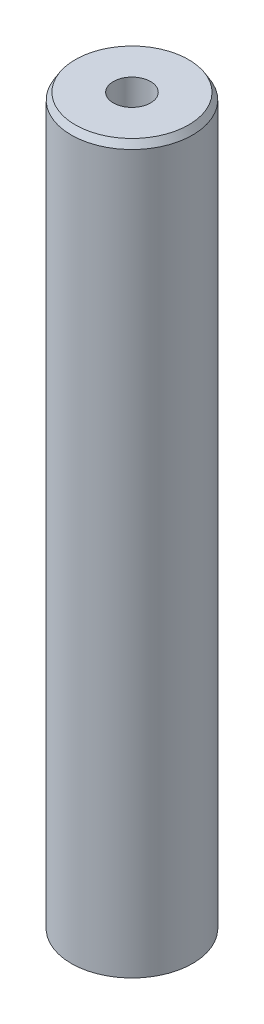
SolidWorks part; units mm, degrees
ref_plane "Front Plane" through (0, 0, 0) normal (0, 0, 1) x (1, 0, 0)
ref_plane "Top Plane" through (0, 0, 0) normal (0, 1, 0) x (1, 0, 0)
ref_plane "Right Plane" through (0, 0, 0) normal (1, 0, 0) x (0, 0, -1)
sketch "Sketch1" plane through (0, 0, 0) normal (0, 1, 0) x (1, 0, 0)
  circle A0 centre (0, 0) radius 50
  dimension "SHAFT_OD" = 100
extrude "Boss-Extrude1" add sketch "Sketch1" along normal blind 600
sketch "Sketch2" plane through (0, 0, 0) normal (0, 1, 0) x (1, 0, 0)
  circle A0 centre (0, 0) radius 15.3326
  dimension "BORE_D" = 30.6652
extrude "Cut-Extrude1" cut sketch "Sketch2" along normal through all
chamfer "Chamfer1" distance 5.542 angle 31.045 2 edges at (0, 600, 50) (0, 0, 50) first distance on face at (0, 600, 50) first distance on face at (0, 0, 15.3326)
